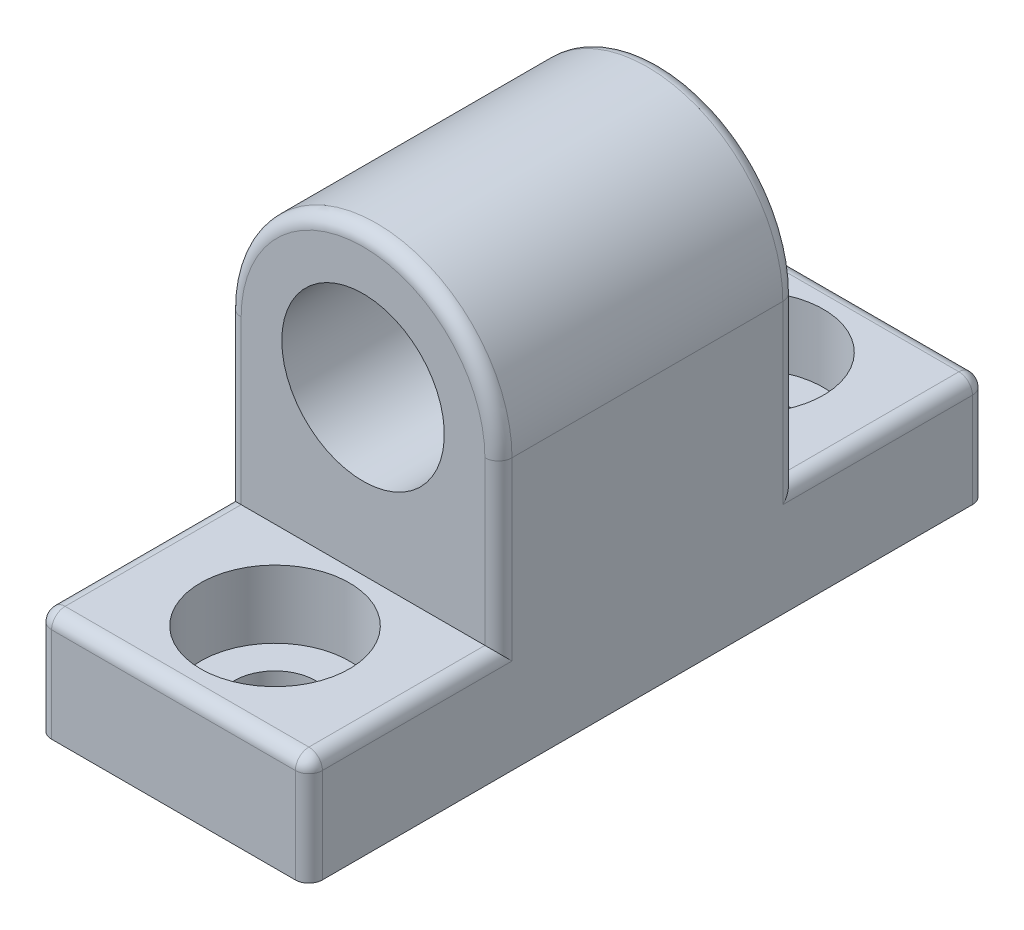
SolidWorks part; units mm, degrees
ref_plane "Спереди" through (0, 0, 0) normal (0, 0, 1) x (1, 0, 0)
ref_plane "Сверху" through (0, 0, 0) normal (0, 1, 0) x (1, 0, 0)
ref_plane "Справа" through (0, 0, 0) normal (1, 0, 0) x (0, 0, -1)
sketch "Эскиз1" plane through (0, 0, 0) normal (0, 0, 1) x (1, 0, 0)
  line L1 (-10, 0) -> (10, 0)
  line L2 (-10, 0) -> (-10, 20)
  line L4 (10, 0) -> (10, 20)
  arc A0 (10, 20) -> (-10, 20) centre (0, 20) ccw
  circle A1 centre (0, 20) radius 6
  dimension "D2" = 30
  dimension "D3" = 12
  dimension "D1" = 20
extrude "Бобышка-Вытянуть1" add sketch "Эскиз1" along normal mid plane 50
sketch "Эскиз2" plane through (0, 0, 0) normal (1, 0, 0) x (0, 0, -1)
  line L0 (-25, 0) -> (25, 0) construction
  line L1 (32.9029, 8) -> (11, 8)
  line L2 (32.9029, 8) -> (32.9029, 39.1917)
  line L3 (32.9029, 39.1917) -> (11, 39.1917)
  line L4 (11, 8) -> (11, 39.1917)
  line L5 (-34.5139, 8) -> (-11, 8)
  line L6 (-34.5139, 8) -> (-34.5139, 41.7756)
  line L7 (-34.5139, 41.7756) -> (-11, 41.7756)
  line L8 (-11, 8) -> (-11, 41.7756)
  line L9 (0, -6.0405) -> (0, 41.7756) construction
  line L10 (25, 20) -> (25, 0) construction
  dimension "D1" = 8
  dimension "D2" = 14
extrude "Вырез-Вытянуть1" cut sketch "Эскиз2" against normal through all and the other way through all
sketch "Эскиз3" plane through (-10, 0, 0) normal (-1, 0, 0) x (0, 0, 1)
  circle A0 centre (0, 20) radius 2.5
  dimension "D1" = 5
  dimension "D2" = 20
extrude "Вырез-Вытянуть2" cut sketch "Эскиз3" against normal up to next
sketch "Эскиз4" plane through (0, 0, 0) normal (0, -1, 0) x (-1, 0, 0)
  circle A0 centre (0, 0) radius 3
  dimension "D1" = 6
extrude "Вырез-Вытянуть3" cut sketch "Эскиз4" against normal blind 12
sketch "Эскиз5" plane through (0, 8, 0) normal (0, 1, 0) x (1, 0, 0)
  line L0 (0, 17.5) -> (0, -17.5) construction
  circle A0 centre (0, 17.5) radius 5.5
  circle A1 centre (0, -17.5) radius 5.5
  dimension "D1" = 11
  dimension "D2" = 35
extrude "Вырез-Вытянуть4" cut sketch "Эскиз5" against normal blind 5
sketch "Эскиз6" plane through (0, 3, 0) normal (0, 1, 0) x (1, 0, 0)
  circle A0 centre (0, 17.5) radius 3
  circle A1 centre (0, -17.5) radius 3
  circle A2 centre (0, 17.5) radius 5.5 construction
  dimension "D1" = 6
extrude "Вырез-Вытянуть5" cut sketch "Эскиз6" against normal through all
fillet "Скругление1" radius 1 16 edges at (10, 14, 11) (10, 14, -11) (10, 8, -18) (10, 4, 25) (-10, 4, 25) (-10, 8, 18) (0, 8, 25) (10, 8, 18) (0, 30, 11) (-10, 14, 11) (-10, 14, -11) (0, 30, -11) (-10, 4, -25) (0, 8, -25) (-10, 8, -18) (10, 4, -25)
ref_plane "Плоскость1" through (0, 0, 0) normal (0, 0, -1) x (-1, 0, 0)
